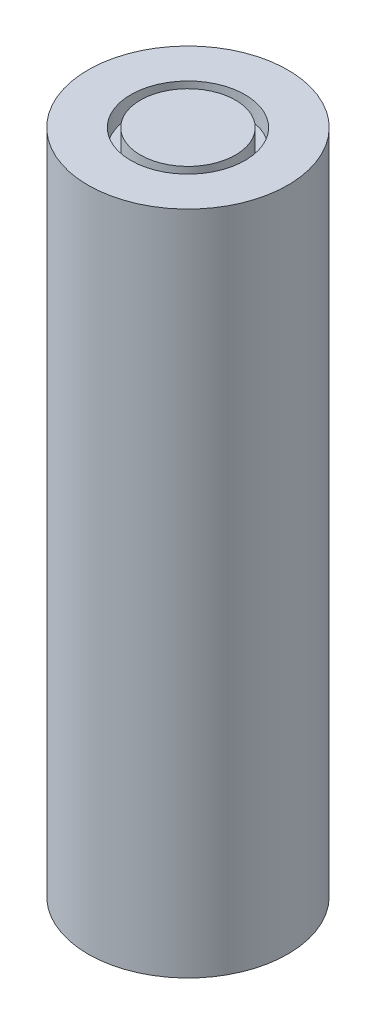
SolidWorks part; units mm, degrees
ref_plane "Спереди" through (0, 0, 0) normal (0, 0, 1) x (1, 0, 0)
ref_plane "Сверху" through (0, 0, 0) normal (0, 1, 0) x (1, 0, 0)
ref_plane "Справа" through (0, 0, 0) normal (1, 0, 0) x (0, 0, -1)
other "Configuration Table"
sketch "Sketch1" plane through (0, 0, 0) normal (0, 1, 0) x (1, 0, 0)
  circle A0 centre (0, 0) radius 10.5
  dimension "D1" = 21
extrude "Boss-Extrude1" add sketch "Sketch1" along normal mid plane 70
sketch "Sketch2" plane through (0, -35, 0) normal (0, -1, 0) x (1, 0, 0)
  circle A0 centre (0, 0) radius 8.5
  circle A1 centre (0, 0) radius 10.5 construction
  dimension "D1" = 2
extrude "Boss-Extrude2" add sketch "Sketch2" along normal mid plane 0.1
sketch "Sketch3" plane through (0, 35, 0) normal (0, 1, 0) x (1, 0, 0)
  circle A0 centre (0, 0) radius 6
  circle A1 centre (0, 0) radius 5
  dimension "D1" = 12
  dimension "D2" = 10
extrude "Cut-Extrude1" cut sketch "Sketch3" against normal blind 2
